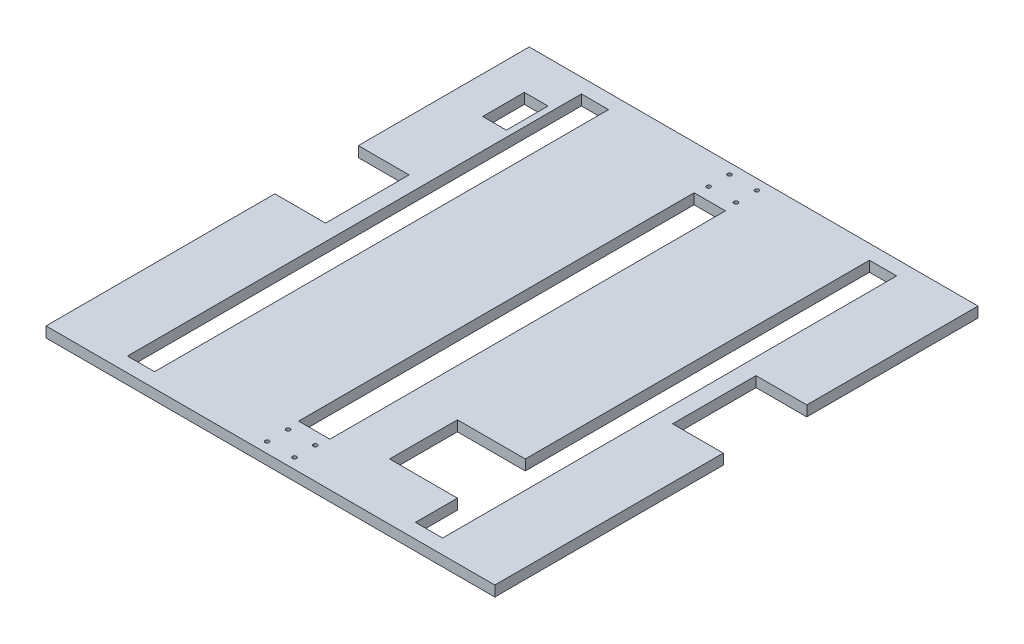
SolidWorks part; units mm, degrees
ref_plane "Front Plane" through (0, 0, 0) normal (0, 0, 1) x (1, 0, 0)
ref_plane "Top Plane" through (0, 0, 0) normal (0, 1, 0) x (1, 0, 0)
ref_plane "Right Plane" through (0, 0, 0) normal (1, 0, 0) x (0, 0, -1)
sketch "Sketch1" plane through (0, 0, 0) normal (0, 1, 0) x (1, 0, 0)
  line L1 (5911.0841, -8489.3124) -> (6341.0841, -8489.3124)
  line L2 (5911.0841, -8489.3124) -> (5911.0841, -8952.3124)
  line L3 (5911.0841, -8952.3124) -> (6341.0841, -8952.3124)
  line L4 (6341.0841, -8489.3124) -> (6341.0841, -8952.3124)
  dimension "D1" = 463
  dimension "D2" = 430
extrude "Boss-Extrude1" add sketch "Sketch1" along normal blind 10
sketch "Sketch2" plane through (0, 10, 0) normal (0, 1, 0) x (1, 0, 0)
  line L0 (5911.0841, -8489.3124) -> (5911.0841, -8952.3124) construction
  line L1 (5959.6841, -8733.0598) -> (5911.0841, -8733.0598)
  line L2 (5959.6841, -8733.0598) -> (5959.6841, -8653.0598)
  line L3 (5959.6841, -8653.0598) -> (5911.0841, -8653.0598)
  line L4 (5911.0841, -8733.0598) -> (5911.0841, -8653.0598)
  line L9 (6341.0841, -8952.3124) -> (6341.0841, -8489.3124) construction
  line L10 (6341.0841, -8733.3844) -> (6292.4841, -8733.3844)
  line L11 (6341.0841, -8733.3844) -> (6341.0841, -8653.3844)
  line L12 (6341.0841, -8653.3844) -> (6292.4841, -8653.3844)
  line L13 (6292.4841, -8733.3844) -> (6292.4841, -8653.3844)
  dimension "D1" = 48.6
  dimension "D2" = 80
  dimension "D3" = 80
  dimension "D4" = 48.6
extrude "Cut-Extrude1" cut sketch "Sketch2" against normal blind 10
sketch "Sketch3" plane through (0, 10, 0) normal (0, 1, 0) x (1, 0, 0)
  line L0 (5975.0841, -8541.6519) -> (5975.0841, -8938.3124)
  line L1 (6277.0841, -8938.3124) -> (6251.0841, -8938.3124)
  line L2 (6277.0841, -8938.3124) -> (6277.0841, -8503.3124)
  line L3 (6277.0841, -8503.3124) -> (6251.0841, -8503.3124)
  line L4 (6251.0841, -8938.3124) -> (6251.0841, -8503.3124)
  line L5 (5975.0841, -8503.3124) -> (6001.0841, -8503.3124)
  line L11 (5975.0841, -8938.3124) -> (6001.0841, -8938.3124)
  line L12 (6001.0841, -8503.3124) -> (6001.0841, -8938.3124)
  line L33 (5946.4841, -8529.3124) -> (5969.1312, -8529.3124)
  line L34 (5946.4841, -8529.3124) -> (5946.4841, -8569.3124)
  line L35 (5946.4841, -8569.3124) -> (5969.1312, -8569.3124)
  line L36 (5911.0841, -8733.0598) -> (5911.0841, -8952.3124) construction
  line L37 (6341.0841, -8952.3124) -> (6341.0841, -8733.3844) construction
  line L38 (5969.1312, -8529.3124) -> (5969.1312, -8569.3124)
  line L39 (6111.0841, -8531.3124) -> (6141.0841, -8531.3124)
  line L40 (6111.0841, -8531.3124) -> (6111.0841, -8910.3124)
  line L41 (6111.0841, -8910.3124) -> (6141.0841, -8910.3124)
  line L42 (6141.0841, -8531.3124) -> (6141.0841, -8910.3124)
  line L44 (6341.0841, -8489.3124) -> (5911.0841, -8489.3124) construction
  line L45 (5975.0841, -8503.3124) -> (5975.0841, -8541.6519)
  line L47 (5911.0841, -8952.3124) -> (6341.0841, -8952.3124) construction
  circle A0 centre (6112.9841, -8942.3124) radius 1.9
  circle A1 centre (6139.1841, -8942.3124) radius 1.9
  circle A2 centre (6112.9841, -8499.3124) radius 1.9
  circle A3 centre (6139.1841, -8499.3124) radius 1.9
  circle A4 centre (6112.9841, -8922.3124) radius 1.9
  circle A5 centre (6139.1841, -8922.3124) radius 1.9
  circle A6 centre (6112.9841, -8519.3124) radius 1.9
  circle A7 centre (6139.1841, -8519.3124) radius 1.9
  point P32 (6126.0841, -8489.3124)
  point P33 (6126.0841, -8531.3124)
  dimension "D12" = 10
  dimension "D13" = 10
  dimension "D15" = 42
  dimension "D16" = 20
  dimension "D18" = 20
  dimension "D1" = 26
  dimension "D2" = 435
  dimension "D3" = 26
  dimension "D4" = 435
  dimension "D5" = 10
  dimension "D6" = 64
  dimension "D7" = 40
  dimension "D8" = 64
  dimension "D9" = 30
  dimension "D10" = 379
  dimension "D11" = 110
  dimension "D14" = 10
  dimension "D17" = 20
  dimension "D19" = 20
  dimension "D20" = 14
  dimension "D21" = 14
extrude "Cut-Extrude2" cut sketch "Sketch3" against normal blind 10
sketch "Sketch4" plane through (0, 10, 0) normal (0, 1, 0) x (1, 0, 0)
  line L0 (6251.0841, -8503.3124) -> (6251.0841, -8938.3124) construction
  line L1 (6251.0841, -8898.0965) -> (6186.0841, -8898.0965)
  line L2 (6251.0841, -8898.0965) -> (6251.0841, -8833.0965)
  line L3 (6251.0841, -8833.0965) -> (6186.0841, -8833.0965)
  line L4 (6186.0841, -8898.0965) -> (6186.0841, -8833.0965)
  dimension "D1" = 65
  dimension "D2" = 65
extrude "Cut-Extrude3" cut sketch "Sketch4" against normal blind 10
ref_plane "Plane1" through (6126.0841, 0, 0) normal (-1, 0, 0) x (0, 0, 1)
